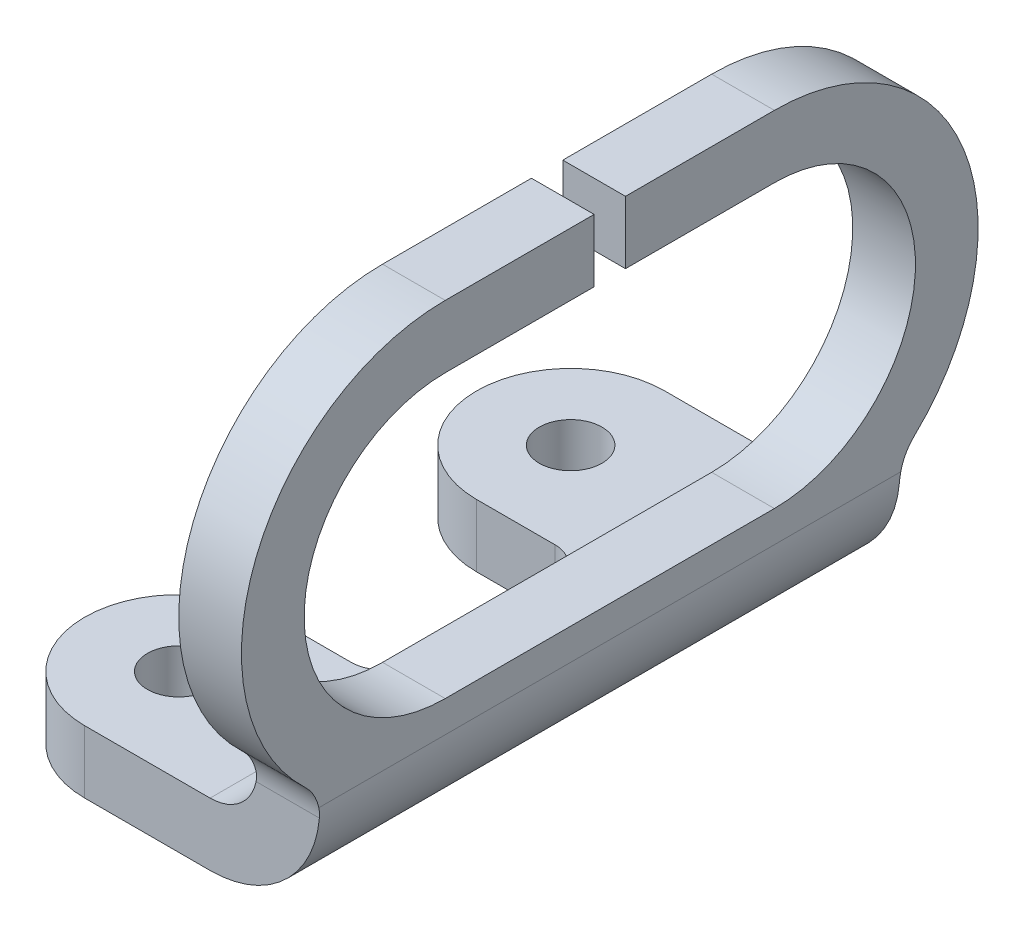
SolidWorks part; units mm, degrees
ref_plane "Front Plane" through (0, 0, 0) normal (0, 0, 1) x (1, 0, 0)
ref_plane "Top Plane" through (0, 0, 0) normal (0, 1, 0) x (1, 0, 0)
ref_plane "Right Plane" through (0, 0, 0) normal (1, 0, 0) x (0, 0, -1)
sketch "Sketch1" plane through (0, 0, 0) normal (0, 1, 0) x (1, 0, 0)
  line L0 (22.648, 0) -> (22.648, 12.5)
  line L1 (0, 0) -> (49.3027, 0)
  line L2 (0, 0) -> (0, 35.2162)
  line L3 (0, 35.2162) -> (49.3027, 35.2162)
  line L4 (49.3027, 0) -> (49.3027, 35.2162)
  line L5 (16.648, 12.5) -> (16.648, -12.5)
  line L6 (22.648, 18.5) -> (37.648, 18.5)
  line L7 (37.648, 28) -> (37.648, -28)
  line L8 (33.648, 28) -> (33.648, -28)
  line L9 (22.648, -18.5) -> (37.648, -18.5)
  line L10 (29.648, 6.5) -> (29.648, -6.5)
  line L11 (22.648, 6.5) -> (29.648, 6.5)
  line L12 (22.648, -6.5) -> (29.648, -6.5)
  line L13 (33.648, 28) -> (37.648, 28)
  line L14 (33.648, -28) -> (37.648, -28)
  circle A0 centre (22.648, 12.5) radius 2
  circle A1 centre (22.648, 12.5) radius 6
  circle A2 centre (22.648, -12.5) radius 2
  circle A3 centre (22.648, -12.5) radius 6
  point P20 (34.6513, 0)
  point P21 (30.6513, 0)
  point P25 (29.648, 0)
  dimension "D2" = 12
  dimension "D6" = 4
  dimension "D1" = 12.5
  dimension "D3" = 4
  dimension "D4" = 28
  dimension "D5" = 11
extrude "Boss-Extrude1" add sketch "Sketch1" along normal blind 4 contours A1 L11 L10 L1 L8 L6 | L12 A3 L9 L8 L1 L10 | A1 A0 | A3 A2 region at (30.6913, 0, -10.1294) region at (18.5253, 0, -8.3774) region at (30.6913, 0, 10.1294) region at (18.5253, 0, 8.3774)
extrude "Boss-Extrude2" add sketch "Sketch1<3>" along normal blind 35 contours L6 L8 L1 L7 | L8 L9 L7 L1 | L13 L8 L6 L7 | L8 L14 L7 L9 region at (35.648, 0, -9.25) region at (35.648, 0, 9.25) region at (35.648, 0, -23.25) region at (35.648, 0, 23.25)
sketch "Sketch1<3>" plane through (0, 0, 0) normal (0, 1, 0) x (1, 0, 0) same geometry as "Sketch1"
sketch "Sketch2" plane through (33.648, 0, 0) normal (-1, 0, 0) x (0, 0, 1)
  line L0 (0, 37.9852) -> (0, -11.2837)
  line L2 (-26, 8) -> (27.6832, 8)
  line L3 (-18.5, 4) -> (18.5, 4) construction
  line L4 (-26, 31) -> (-26, 8)
  line L5 (-12.5, 18) -> (12.5, 18)
  line L6 (-12.5, 18) -> (-12.5, 10.5)
  line L7 (0, 10.5) -> (-20, 10.5)
  line L8 (-26, 31) -> (26, 31)
  line L9 (35.9199, 37.9852) -> (-35.9199, 37.9852)
  line L10 (-35.9199, 37.9852) -> (-35.9199, -11.2837)
  line L11 (-35.9199, -11.2837) -> (35.9199, -11.2837)
  line L12 (26, 8) -> (-27.6832, 8)
  line L13 (26, 31) -> (26, 8)
  line L14 (35.9199, 37.9852) -> (35.9199, -11.2837)
  line L15 (18.5, 4) -> (-18.5, 4)
  line L16 (-18.5, 4) -> (-18.5, 8)
  line L17 (18.5, 4) -> (18.5, 8)
  line L18 (-12.5, 18) -> (-12.5, 26.5)
  line L19 (-18.5, 4) -> (-22.3095, 5.9321)
  line L22 (18.5, 4) -> (22.3095, 5.9321)
  circle A0 centre (-12.5, 18) radius 8.5
  circle A1 centre (12.5, 18) radius 8.5
  circle A2 centre (-20.5, 26.5) radius 1
  circle A3 centre (-20.5, 9.5) radius 1
  circle A4 centre (-20.5, 26.5) radius 4.2483
  circle A5 centre (-20.5, 9.5) radius 4.0006
  circle A6 centre (20.5, 9.5) radius 1
  circle A7 centre (20.5, 9.5) radius 4.0006
  circle A8 centre (20.5, 26.5) radius 1
  circle A9 centre (20.5, 26.5) radius 4.2483
  arc A11 (0, 18) -> (-17.4642, 29.472) centre (-12.5, 18) ccw
  arc A12 (-23.6503, 23.6498) -> (-23.5278, 12.1147) centre (-12.5, 18) ccw
  arc A13 (23.6503, 23.6498) -> (23.5278, 12.1147) centre (12.5, 18) cw
  arc A14 (0, 18) -> (17.4642, 29.472) centre (12.5, 18) cw
  point P20 (0, 31)
  point P29 (0, 4)
  point P39 (0, 18)
  dimension "D5" = 14
  dimension "D6" = 17
  dimension "D9" = 20.5
  dimension "D11" = 12.5
  dimension "D1" = 4
  dimension "D2" = 23
  dimension "D3" = 26
  dimension "D4" = 12.5
  dimension "D7" = 20
  dimension "D10" = 8.5
fillet "Fillet3" radius 2 2 edges at (29.648, 2, -6.5) (29.648, 2, 6.5)
sketch "Sketch3" plane through (37.648, 0, 0) normal (1, 0, 0) x (0, 0, -1)
  line L0 (0, 0) -> (0, 35)
  line L1 (28, 35) -> (-28, 35) construction
  line L2 (0, 18) -> (19.5, 18)
  line L3 (0, 27) -> (10.5, 27)
  line L4 (0, 31) -> (10.5, 31)
  line L5 (10.5, 9) -> (0, 9)
  line L6 (10.5, 5) -> (0, 5)
  line L7 (-10.5, 5) -> (0, 5)
  line L8 (-10.5, 9) -> (0, 9)
  line L9 (0, 27) -> (-10.5, 27)
  line L10 (0, 31) -> (-10.5, 31)
  line L11 (18.5, 0) -> (18.5, 7.753)
  line L12 (-18.5, 0) -> (-18.5, 7.753)
  arc A0 (10.5, 9) -> (10.5, 27) centre (10.5, 18) ccw
  arc A1 (10.5, 5) -> (10.5, 31) centre (10.5, 18) ccw
  arc A2 (-10.5, 9) -> (-10.5, 27) centre (-10.5, 18) cw
  arc A3 (-10.5, 5) -> (-10.5, 31) centre (-10.5, 18) cw
  line M8 (-28, 0) -> (28, 0)
  line M9 (28, 0) -> (28, 35)
  line M10 (28, 35) -> (-28, 35)
  line M11 (-28, 35) -> (-28, 0)
  dimension "D2" = 18
  dimension "D1" = 19.5
  dimension "D3" = 18
  dimension "D4" = 4
extrude "Cut-Extrude2" cut sketch "Sketch3" against normal blind 10 contours A2 L8 L0 L9 | L5 A0 L2 L0 | L2 A0 L3 L0 | L12 A3 L10 L0 M10 M11 M8 | A1 L11 L0 L4 M8 M9 M10 region at (37.648, 0.4482, 23.25) region at (37.648, 3.8765, -18.9482) region at (37.648, 18, 8.8991) region at (37.648, 13.7737, -8.8991) region at (37.648, 22.2263, -8.8991)
sketch "Sketch4" plane through (37.648, 0, 0) normal (1, 0, 0) x (0, 0, -1)
  line L0 (10.5, 27) -> (-10.5, 27) construction
  line L1 (-1, 35.3492) -> (1, 35.3492)
  line L2 (-1, 35.3492) -> (-1, 27)
  line L3 (-1, 27) -> (1, 27)
  line L4 (1, 35.3492) -> (1, 27)
  point P4 (0, 27)
  dimension "D1" = 2
extrude "Cut-Extrude3" cut sketch "Sketch4" against normal blind 10
fillet "Fillet4" radius 3 2 edges at (35.648, 7.753, -18.5) (35.648, 7.753, 18.5)
fillet "Fillet6" radius 3 1 edges at (33.648, 4, 0)
fillet "Fillet5" radius 7 1 edges at (37.648, 0, 0)
